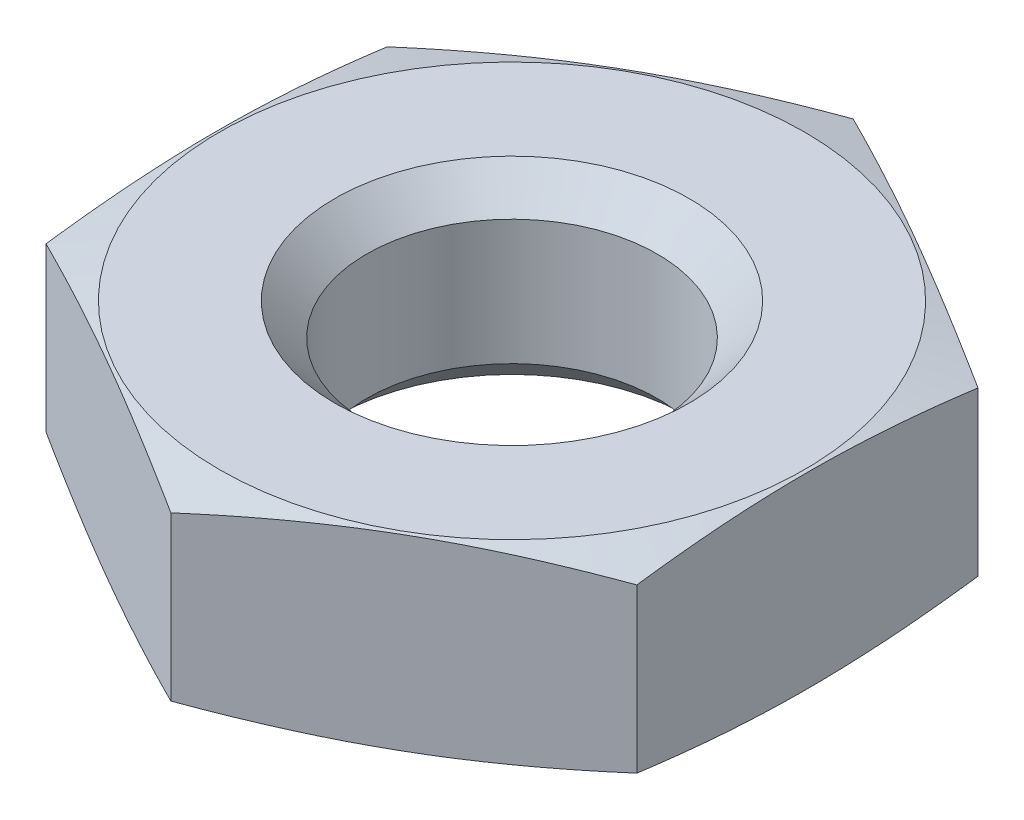
SolidWorks part; units mm, degrees
ref_plane "Front Plane" through (0, 0, 0) normal (0, 0, 1) x (1, 0, 0)
ref_plane "Top Plane" through (0, 0, 0) normal (0, 1, 0) x (1, 0, 0)
ref_plane "Right Plane" through (0, 0, 0) normal (1, 0, 0) x (0, 0, -1)
ref_plane "Plane1" through (0, 0, 0) normal (0, 0, 1) x (1, 0, 0)
sketch "Sketch1" plane through (0, 0, 0) normal (0, 0, 1) x (1, 0, 0)
  line L0 (0, 0) -> (4.95, 0)
  line L1 (4.95, 0) -> (10.9213, -1.6)
  line L2 (10.9213, -1.6) -> (4.95, -3.2)
  line L3 (4.95, -3.2) -> (0, -3.2)
  line L4 (0, -3.2) -> (0, 0)
  line L5 (0, -3.2) -> (0, 0) construction
revolve "Revolve1" add sketch "Sketch1" angle 360 about L5
ref_plane "Plane2" through (0, 0, 0) normal (0, 1, 0) x (1, 0, 0)
sketch "Sketch2" plane through (0, 0, 0) normal (0, 1, 0) x (1, 0, 0)
  line L0 (-20, 20) -> (-20, -20)
  line L1 (-20, -20) -> (20, -20)
  line L2 (20, -20) -> (20, 20)
  line L3 (20, 20) -> (-20, 20)
  line L4 (-5, -2.8868) -> (0, -5.7735)
  line L5 (0, -5.7735) -> (5, -2.8868)
  line L6 (5, -2.8868) -> (5, 2.8868)
  line L7 (5, 2.8868) -> (0, 5.7735)
  line L8 (0, 5.7735) -> (-5, 2.8868)
  line L9 (-5, 2.8868) -> (-5, -2.8868)
extrude "Cut-Extrude1" cut sketch "Sketch2" against normal blind 4.2 and the other way blind 4.2
ref_plane "Plane3" through (0, 0, 0) normal (0, 0, 1) x (1, 0, 0)
sketch "Sketch3" plane through (0, 0, 0) normal (0, 0, 1) x (1, 0, 0)
  line L0 (0, 0) -> (3, 0)
  line L1 (3, 0) -> (2.4585, -0.5415)
  line L2 (2.4585, -0.5415) -> (2.4585, -2.6585)
  line L3 (2.4585, -2.6585) -> (3, -3.2)
  line L4 (3, -3.2) -> (0, -3.2)
  line L5 (0, -3.2) -> (0, 0)
  line L6 (0, -3.2) -> (0, 0) construction
revolve "Cut-Revolve1" cut sketch "Sketch3" angle 360 about L6 reverse direction yes
cosmetic thread "Cosmetic Thread1" parameters "D1"=3.2, "D2"=6
